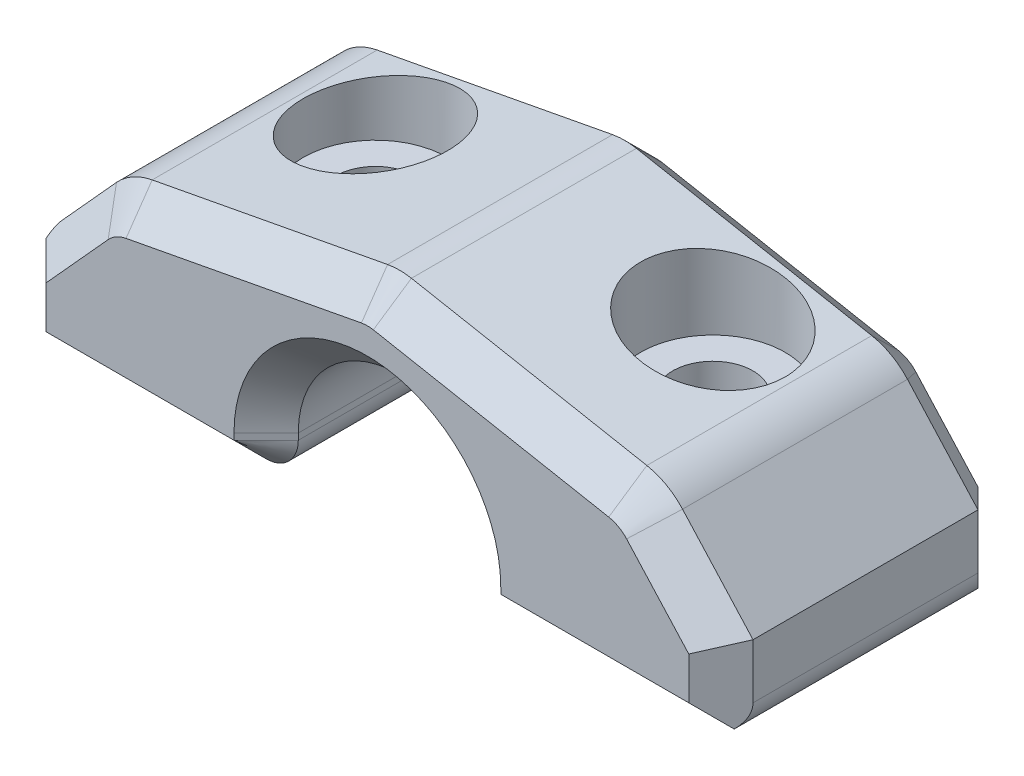
SolidWorks part; units mm, degrees
ref_plane "Front Plane" through (0, 0, 0) normal (0, 0, 1) x (1, 0, 0)
ref_plane "Top Plane" through (0, 0, 0) normal (0, 1, 0) x (1, 0, 0)
ref_plane "Right Plane" through (0, 0, 0) normal (1, 0, 0) x (0, 0, -1)
sketch "Sketch1" plane through (0, 0, 0) normal (0, 0, 1) x (1, 0, 0)
  line L0 (-3.15, 0) -> (-11, 0)
  line L1 (-11, 0) -> (-11, 6)
  line L2 (-11, 6) -> (11, 6)
  line L3 (0, 6) -> (0, 3.3) construction
  line L4 (11, 0) -> (11, 6)
  line L5 (3.15, 0) -> (11, 0)
  arc A0 (3.15, 0) -> (-3.15, 0) centre (0, 0) ccw
  dimension "D1" = 6.3
  dimension "D2" = 22
  dimension "D3" = 6
extrude "Boss-Extrude1" add sketch "Sketch1" along normal blind 9
sketch "Sketch2" plane through (0, 0, 9) normal (0, 0, 1) x (1, 0, 0)
  line L0 (0, 6) -> (-8.3557, 4.4229)
  line L1 (11, 6) -> (-11, 6) construction
  line L2 (-8.3557, 4.4229) -> (-11, 1.5044)
  line L3 (-11, 6) -> (-11, 0) construction
  line L4 (-11, 1.5044) -> (-11, 6)
  line L5 (-11, 6) -> (11, 6)
  line L6 (0, 8.1862) -> (0, -3.9101) construction
  line L7 (11, 1.5044) -> (11, 6)
  line L8 (8.3557, 4.4229) -> (11, 1.5044)
  line L9 (0, 6) -> (8.3557, 4.4229)
  line L10 (-11, 0) -> (-3.15, 0) construction
  line M8 (11, 0) -> (11, 6)
  line M9 (11, 6) -> (-11, 6)
  line M10 (-11, 6) -> (-11, 0)
  dimension "D1" = 4.4229
  dimension "D2" = 16.7114
  dimension "D3" = 4.4956
extrude "Cut-Extrude1" cut sketch "Sketch2" against normal through all both and the other way through all contours L2 L0 M9 M10 | L9 L8 M9 M8 region at (-7.9428, 4.865, 9) region at (7.9428, 4.865, 9)
sketch "Sketch3" plane through (0, 0, 9) normal (0, 0, 1) x (1, 0, 0)
  line L0 (-3.15, 0) -> (-3.15, -1.1963)
  line L1 (-3.15, -1.1963) -> (-11, -1.1963)
  line L2 (-11, -1.1963) -> (-11, 0)
  line L3 (-11, 0) -> (-3.15, 0)
  line L4 (0, 2.4166) -> (0, -1.9705) construction
  line L5 (11, 0) -> (3.15, 0)
  line L6 (11, -1.1963) -> (11, 0)
  line L7 (3.15, -1.1963) -> (11, -1.1963)
  line L8 (3.15, 0) -> (3.15, -1.1963)
extrude "Boss-Extrude2" add sketch "Sketch3" against normal up to surface (9 mm away) up to face at (0, 2.3339, 0)
chamfer "Chamfer1" distance 1 angle 45 4 edges at (-11, 0.1541, 0) (11, 0.1541, 0) (11, 0.1541, 9) (-11, 0.1541, 9)
fillet "Fillet1" radius 1 2 edges at (3.15, -1.1963, 4.5) (-3.15, -1.1963, 4.5)
sketch "Sketch4" plane through (0, -1.1963, 0) normal (0, -1, 0) x (1, 0, 0)
  line L0 (0, 10.0567) -> (0, -3.4815) construction
  line L1 (-5.25, 3.5) -> (5.25, 3.5) construction
  line L2 (-3.15, 0) -> (3.15, 0) construction
  circle A0 centre (-5.25, 3.5) radius 1.25
  circle A1 centre (5.25, 3.5) radius 1.25
  point P7 (6.768, 1.3051)
  point P8 (0, 3.5)
  dimension "D2" = 2.5
  dimension "D1" = 10.5
  dimension "D3" = 3.5
extrude "Cut-Extrude2" cut sketch "Sketch4" against normal through all
sketch "Sketch5" plane through (0, 0, 0) normal (0, 1, 0) x (1, 0, 0)
  circle A0 centre (-5.25, -3.5) radius 2.25
  circle A1 centre (5.25, -3.5) radius 2.25
  dimension "D1" = 4.5
extrude "Cut-Extrude3" cut sketch "Sketch5" along normal blind 10 from offset 3
fillet "Fillet2" radius 2 4 edges at (8.3557, 4.4229, 4.5) (-8.3557, 4.4229, 4.5) (-11, 1.5044, 4.5)
fillet "Fillet3" radius 1 2 edges at (11, -1.1963, 4.5) (-11, -1.1963, 4.5)
chamfer "Chamfer2" distance 1 angle 45 28 edges at (-9.4034, 3.2666, 0) (-8.302, 4.3271, 0) (-4.0333, 5.2388, 0) (9.4034, 3.2666, 0) (0, 5.9647, 0) (8.302, 4.3271, 0) (4.0333, 5.2388, 0) (-7.075, -1.1963, 0) (7.075, -1.1963, 0) (-3.4429, -0.9034, 0) (3.4429, -0.9034, 0) (-3.15, -0.0982, 0) (3.15, -0.0982, 0) (0, 3.15, 0) (-7.075, -1.1963, 9) (7.075, -1.1963, 9) (-3.4429, -0.9034, 9) (3.4429, -0.9034, 9) (-3.15, -0.0982, 9) (3.15, -0.0982, 9) (0, 3.15, 9) (9.4034, 3.2666, 9) (8.302, 4.3271, 9) (-9.4034, 3.2666, 9) (0, 5.9647, 9) (-8.302, 4.3271, 9)
